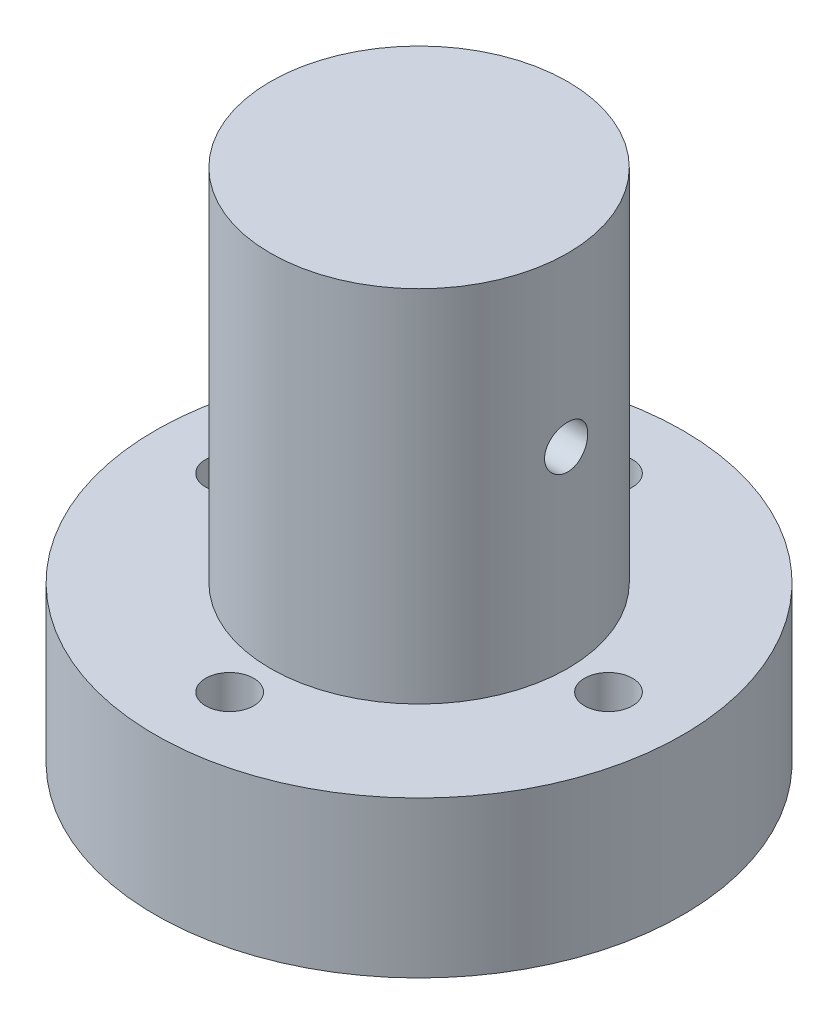
SolidWorks part; units mm, degrees
ref_plane "Front Plane" through (0, 0, 0) normal (0, 0, 1) x (1, 0, 0)
ref_plane "Top Plane" through (0, 0, 0) normal (0, 1, 0) x (1, 0, 0)
ref_plane "Right Plane" through (0, 0, 0) normal (1, 0, 0) x (0, 0, -1)
sketch "Sketch1" plane through (0, 0, 0) normal (0, 1, 0) x (1, 0, 0)
  circle A1 centre (0, 0) radius 11
  dimension "D1" = 22
extrude "Boss-Extrude1" add sketch "Sketch1" along normal blind 6.5
sketch "Sketch2" plane through (0, 6.5, 0) normal (0, 1, 0) x (1, 0, 0)
  line L0 (0, 0) -> (0, 7.9) construction
  line L1 (0, 0) -> (7.1319, 0) construction
  circle A0 centre (0, 7.9) radius 1
  point P4 (0, 6.9)
  point P5 (0, 8.9)
  point P7 (0, 8.9)
  dimension "D1" = 13.8
  dimension "D2" = 17.8
extrude "Cut-Extrude1" cut sketch "Sketch2" against normal through all
ref_axis "Axis1" through (0, 6.5, 0) along (0, -1, 0)
pattern_circular "CirPattern1" count 4 over 360 about axis through (0, 6.5, 0) along (0, -1, 0) of "Cut-Extrude1"
sketch "Sketch3" plane through (0, 6.5, 0) normal (0, 1, 0) x (1, 0, 0)
  circle A0 centre (0, 0) radius 6.2
  dimension "D1" = 12.4
extrude "Boss-Extrude2" add sketch "Sketch3" along normal blind 15
sketch "Sketch4" plane through (0, 0, 0) normal (1, 0, 0) x (0, 0, -1)
  line L0 (0, 6.5) -> (0, 0) construction
  line L1 (6.2, 6.5) -> (-6.2, 6.5) construction
  circle A0 centre (0, 14.5) radius 0.9
  dimension "D1" = 1.8
  dimension "D2" = 8
extrude "Cut-Extrude2" cut sketch "Sketch4" against normal through all both and the other way through all
